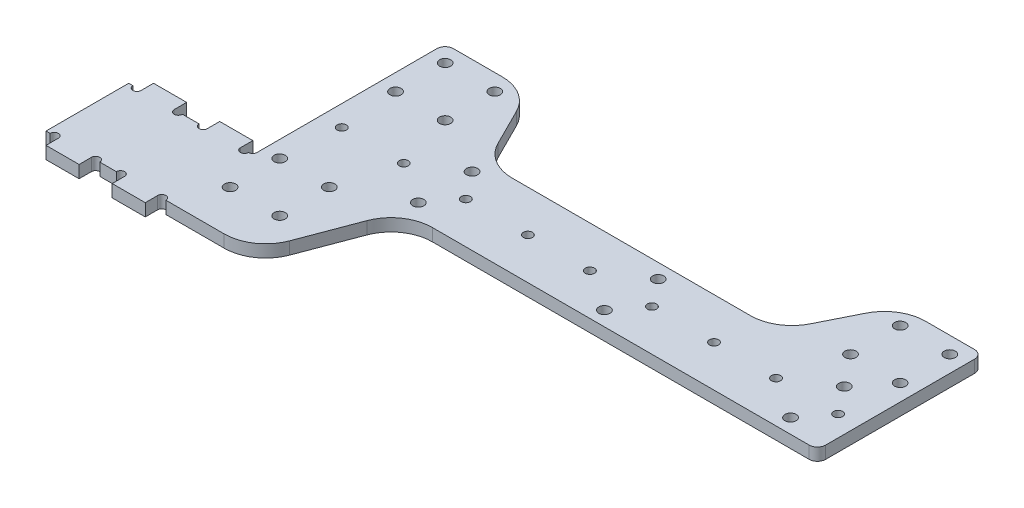
SolidWorks part; units mm, degrees
material "碳纤维"
ref_plane "前视基准面" through (0, 0, 0) normal (0, 0, 1) x (1, 0, 0)
ref_plane "上视基准面" through (0, 0, 0) normal (0, 1, 0) x (1, 0, 0)
ref_plane "右视基准面" through (0, 0, 0) normal (1, 0, 0) x (0, 0, -1)
sketch "草图1" plane through (0, 0, 0) normal (0, 1, 0) x (1, 0, 0)
  line L0 (10, 10) -> (10, 30)
  line L1 (-10, -36.5) -> (10, -36.5)
  line L2 (-10, -36.5) -> (-10, 30)
  line L4 (10, -36.5) -> (10, -10)
  line L5 (0, 30) -> (0, -36.5) construction
  line L6 (-10, 0) -> (10, 0) construction
  line L11 (10, 10) -> (100, 10)
  line L13 (10, -10) -> (120, -10)
  line L14 (120, 10) -> (120, -10)
  line L15 (65, -10) -> (65, 10) construction
  line L16 (10, 0) -> (120, 0) construction
  line L17 (-10, 30) -> (10, 30)
  line L24 (120, 10) -> (120, 30)
  line L25 (120, 30) -> (100, 30)
  line L26 (100, 10) -> (100, 30)
  point P0 (0, 0)
  point P86 (65, 0)
  dimension "D1" = 110
  dimension "D2" = 20
  dimension "D3" = 36.5
  dimension "D4" = 30
extrude "凸台-拉伸1" add sketch "草图1" along normal blind 3
sketch "草图2" plane through (0, 3, 0) normal (0, 1, 0) x (1, 0, 0)
  line L0 (0, 35.3457) -> (0, 0) construction
  line L1 (10, -10) -> (120, -10) construction
  line L2 (10, 20) -> (-10, 20) construction
  line L4 (100, 10) -> (10, 10) construction
  line L5 (0, 0) -> (120, 0) construction
  line L6 (120, -10) -> (120, 30) construction
  line L7 (65, 10) -> (65, -10) construction
  line L8 (100, 10) -> (10, 10) construction
  line L9 (55, 10) -> (55, 32.4367) construction
  line L10 (100, 10) -> (10, 10) construction
  circle A0 centre (-6, 26) radius 1.35
  circle A1 centre (-6, 14) radius 1.35
  circle A2 centre (6, 14) radius 1.35
  circle A3 centre (6, 26) radius 1.35
  circle A4 centre (6, -26) radius 1.35
  circle A5 centre (6, -14) radius 1.35
  circle A6 centre (-6, -14) radius 1.35
  circle A7 centre (-6, -26) radius 1.35
  circle A8 centre (110, 6.5) radius 1.35
  circle A10 centre (20, 6.5) radius 1.35
  circle A11 centre (65, 6.5) radius 1.35
  circle A12 centre (65, -6.5) radius 1.35
  circle A13 centre (20, -6.5) radius 1.35
  circle A14 centre (110, -6.5) radius 1.35
  circle A19 centre (104, 26) radius 1.35
  circle A20 centre (104, 14) radius 1.35
  circle A21 centre (116, 14) radius 1.35
  circle A22 centre (116, 26) radius 1.35
  dimension "D3" = 2.7
  dimension "D4" = 10
  dimension "D1" = 12
  dimension "D2" = 12
  dimension "D5" = 3.5
  dimension "D6" = 10
extrude "切除-拉伸1" cut sketch "草图2" against normal through all
sketch "草图3" plane through (0, 3, 0) normal (0, 1, 0) x (1, 0, 0)
  line L0 (120, -10) -> (120, 30) construction
  line L1 (0, 0) -> (115, 0) construction
  circle A14 centre (115, 0) radius 1.1
  circle A15 centre (100, 0) radius 1.1
  circle A16 centre (85, 0) radius 1.1
  circle A17 centre (70, 0) radius 1.1
  circle A18 centre (55, 0) radius 1.1
  circle A19 centre (40, 0) radius 1.1
  circle A20 centre (25, 0) radius 1.1
  circle A21 centre (10, 0) radius 1.1
  circle A22 centre (-5, 0) radius 1.1
  dimension "D3" = 15
  dimension "D1" = 5
  dimension "D2" = 2.2
extrude "切除-拉伸2" cut sketch "草图3" against normal through all
sketch "草图4" plane through (0, 3, 0) normal (0, 1, 0) x (1, 0, 0)
  line L1 (-10, -36.5) -> (-40, -36.5)
  line L2 (-10, -36.5) -> (-10, -16.5)
  line L3 (-10, -16.5) -> (-40, -16.5)
  line L4 (-40, -36.5) -> (-40, -16.5)
  line L5 (-25, -16.5) -> (-25, -36.5) construction
  line L6 (-10, -26.5) -> (-40, -26.5) construction
  point P108 (-25, -26.5)
  dimension "D1" = 20
  dimension "D2" = 30
extrude "凸台-拉伸2" add sketch "草图4" against normal up to surface (3 mm away) up to face at (115, 0, 1.1)
sketch "草图5" plane through (0, 0, 0) normal (0, -1, 0) x (1, 0, 0)
  line L0 (-25, 16.5) -> (-25, 36.5) construction
  line L1 (-40, 16.5) -> (-10, 16.5) construction
  line L2 (-40, 36.5) -> (10, 36.5) construction
  line L3 (-40, 26.5) -> (-25, 26.5) construction
  line L8 (-13, 16.5) -> (-21, 16.5)
  line L9 (-37, 13.5) -> (-29, 13.5)
  line L10 (-40, 36.5) -> (-40, 16.5) construction
  line L15 (-37, 13.5) -> (-37, 16.5)
  line L16 (-37, 16.5) -> (-29, 16.5)
  line L17 (-29, 13.5) -> (-29, 16.5)
  line L18 (-33, 16.5) -> (-33, 13.5) construction
  line L19 (-37, 15) -> (-29, 15) construction
  line L20 (-21, 13.5) -> (-21, 16.5)
  line L21 (-13, 13.5) -> (-21, 13.5)
  line L22 (-13, 13.5) -> (-13, 16.5)
  line L23 (-37, 36.5) -> (-29, 36.5)
  line L24 (-29, 39.5) -> (-29, 36.5)
  line L25 (-37, 39.5) -> (-29, 39.5)
  line L26 (-37, 39.5) -> (-37, 36.5)
  line L27 (-13, 39.5) -> (-13, 36.5)
  line L28 (-13, 39.5) -> (-21, 39.5)
  line L29 (-21, 39.5) -> (-21, 36.5)
  line L30 (-13, 36.5) -> (-21, 36.5)
  point P6 (-33, 15)
  dimension "D1" = 3
  dimension "D2" = 8
  dimension "D3" = 24
extrude "凸台-拉伸3" add sketch "草图5" against normal up to surface (3 mm away) up to face at (115, 3, 1.1)
sketch "草图6" plane through (0, 0, 0) normal (0, -1, 0) x (1, 0, 0)
  line L0 (-13, 16.5) -> (-10, 16.5) construction
  line L2 (-17, 13.5) -> (-17, 16.5) construction
  line L3 (-21, 13.5) -> (-13, 13.5) construction
  line L4 (-25, 16.5) -> (-25, 36.5) construction
  line L5 (-29, 16.5) -> (-21, 16.5) construction
  line L6 (-29, 36.5) -> (-21, 36.5) construction
  line L7 (-25, 26.5) -> (-40, 26.5) construction
  line L8 (-40, 36.5) -> (-40, 16.5) construction
  circle A0 centre (-12, 16.5) radius 1
  circle A2 centre (-22, 16.5) radius 1
  circle A3 centre (-38, 16.5) radius 1
  circle A4 centre (-28, 16.5) radius 1
  circle A5 centre (-28, 36.5) radius 1
  circle A6 centre (-38, 36.5) radius 1
  circle A7 centre (-22, 36.5) radius 1
  circle A8 centre (-12, 36.5) radius 1
  dimension "D1" = 2
extrude "切除-拉伸3" cut sketch "草图6" against normal through all
fillet "圆角1" radius 1 1 edges at (-10, 1.5, 16.5)
sketch "草图9" plane through (0, 3, 0) normal (0, 1, 0) x (1, 0, 0)
  line L0 (10, -36.5) -> (20, -10)
  line L1 (10, -10) -> (120, -10) construction
  line L2 (20, -10) -> (10, -10)
  line L3 (10, -10) -> (10, -36.5)
  line L4 (0, 0) -> (-10, 0) construction
  line L5 (-10, 30) -> (-10, -15.5) construction
  line L6 (20, 10) -> (10, 10)
  line L7 (10, 30) -> (20, 10)
  line L8 (10, 10) -> (10, 30)
  line L9 (10, 10) -> (10, 30) construction
  line L10 (10, 30) -> (-10, 30) construction
  line L11 (55, 10) -> (55, 31.1414) construction
  line L16 (100, 10) -> (10, 10) construction
  line L17 (100, 30) -> (90, 10)
  line L18 (100, 10) -> (100, 30)
  line L19 (90, 10) -> (100, 10)
  dimension "D1" = 10
extrude "凸台-拉伸5" add sketch "草图9" against normal up to surface (3 mm away) up to face at (-6.1054, 0, 17.2558)
fillet "圆角3" radius 10 6 edges at (10, 1.5, 36.5) (20, 1.5, 10) (20, 1.5, -10) (10, 1.5, -30) (90, 1.5, -10) (100, 1.5, -30)
fillet "圆角4" radius 2 3 edges at (120, 1.5, 10) (-10, 1.5, -30) (120, 1.5, -30)
